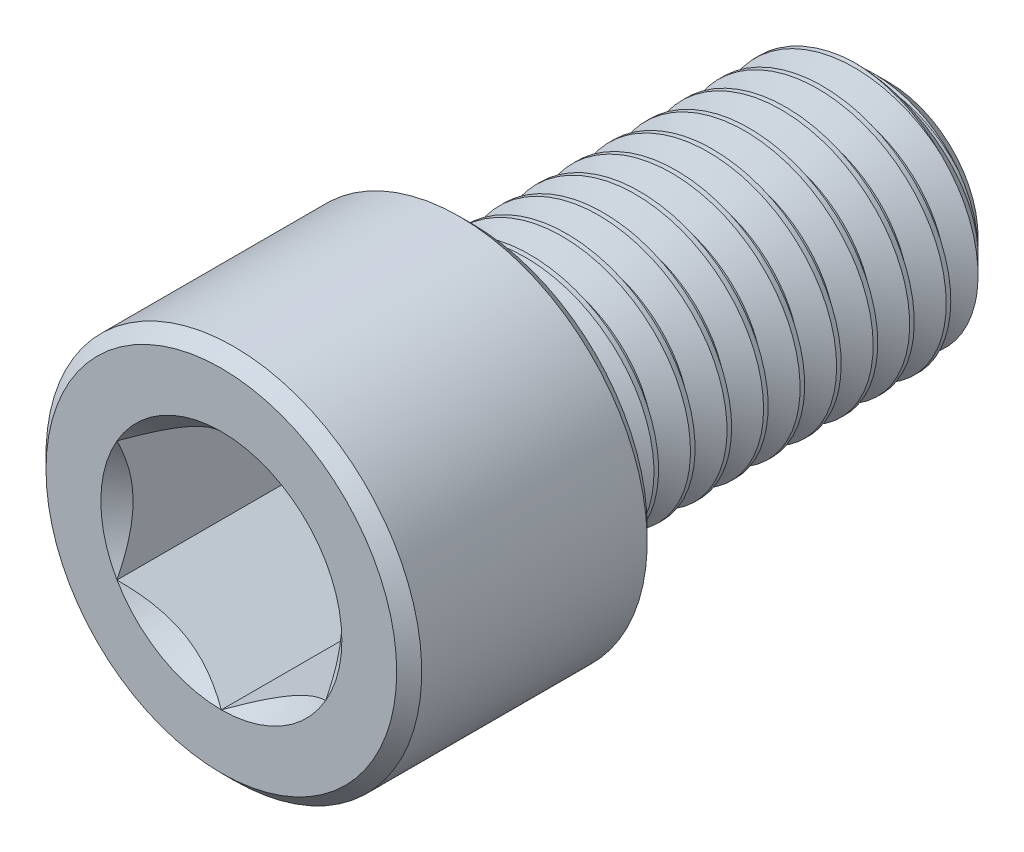
SolidWorks part; units mm, degrees
ref_plane "Front Plane" through (0, 0, 0) normal (0, 0, 1) x (1, 0, 0)
ref_plane "Top Plane" through (0, 0, 0) normal (0, 1, 0) x (1, 0, 0)
ref_plane "Right Plane" through (0, 0, 0) normal (1, 0, 0) x (0, 0, -1)
sketch "Sketch1" plane through (0, 0, 0) normal (1, 0, 0) x (0, 0, -1)
  line L0 (-16, 0) -> (16, 0) construction
  line L1 (16, 0) -> (16, 4.25) construction
  line L2 (16, 4.25) -> (14.25, 6) construction
  line L3 (14.25, 6) -> (14.6875, 6) construction
  line L4 (14.6875, 6) -> (-4, 6) construction
  line L5 (-4, 6) -> (-4, 9) construction
  line L6 (-4, 9) -> (-16, 9) construction
  line L7 (-16, 9) -> (-16, 0) construction
  line L8 (16, 4.25) -> (16, 6) construction
  line L9 (15.8906, 6.1894) -> (16.7656, 4.6739) construction
  line L10 (16.7656, 4.6739) -> (17.6406, 6.1894) construction
  line L11 (17.6406, 6.1894) -> (15.8906, 6.1894) construction
  line L12 (16.7656, 6.1894) -> (16.7656, 6) construction
  line L13 (16.7656, 4.6739) -> (16.7656, 4.8633) construction
  line L14 (16.6562, 4.8633) -> (16.875, 4.8633) construction
  line L15 (16, 6) -> (17.5312, 6) construction
  line L16 (15.9453, 6.0947) -> (17.5859, 6.0947) construction
  line L17 (16, 0) -> (16, -6) construction
  line L18 (-4.6, 9) -> (-4, 8.4) construction
  line L19 (-15.4, 9) -> (-16, 8.4) construction
  line L20 (-4, 6) -> (-4, 0) construction
  line L21 (-4, 3) -> (2.6667, 3) construction
  line L22 (2.6667, 3) -> (9.3333, 3) construction
  line L23 (9.3333, 3) -> (16, 3) construction
  line L24 (2.6667, 3) -> (2.6667, 6) construction
  line L25 (2.6667, 6) -> (2.6667, 9) construction
  line L26 (9.3333, 3) -> (9.3333, 9) construction
  point P0 (-16, 5)
  point P3 (11.625, 6)
  point P4 (0, 0)
  point P18 (9.3333, 6)
  point P22 (16.7656, 4.8633)
  point P24 (14.6875, 6)
  point P25 (16.7656, 6)
  point P28 (16.7656, 6.0947)
  point P29 (11.625, -6)
  point P30 (2.6667, 6)
  point P31 (-10, 9)
  point P37 (-6.1, 9)
  point P38 (-15.1, 9)
  point P45 (2.6667, 3)
  point P46 (9.3333, 3)
  dimension "D1" = 45
  dimension "D2" = 0.2188
  dimension "D3" = 1.75
  dimension "D7" = 0.6
  dimension "D8" = 0.6
  dimension "D9" = 0.6
  dimension "D10" = 0.3
  dimension "D11" = 1.5
  dimension "Drive Size" = 10
  dimension "Head Diameter" = 18
  dimension "Head Height" = 12
  dimension "Thread Pitch" = 1.75
  dimension "Thread Major Diameter" = 12
  dimension "Length" = 20
  dimension "D12" = 1.3125
  dimension "D4" = 4.375
sketch "Sketch2" plane through (0, 0, 0) normal (1, 0, 0) x (0, 0, -1)
  line L0 (-16, 0) -> (-16, 8.4)
  line L1 (-15.4, 9) -> (-4.6, 9)
  line L2 (-4, 8.4) -> (-4, 6)
  line L3 (-4, 6) -> (14.25, 6)
  line L4 (14.25, 6) -> (16, 4.25)
  line L5 (16, 4.25) -> (16, 0)
  line L6 (-4.6, 9) -> (-4, 8.4) construction
  line L7 (16, 0) -> (-16, 0)
  line L8 (-15.4, 9) -> (-16, 8.4) construction
  line L9 (-4.6, 9) -> (-4, 8.4)
  line L10 (-15.4, 9) -> (-16, 8.4)
revolve "Revolve1" add sketch "Sketch2" angle 360 about L7
sketch "Sketch3" plane through (0, 0, 16) normal (0, 0, 1) x (1, 0, 0)
  line L1 (5, -2.8868) -> (5, 2.8868)
  line L2 (5, 2.8868) -> (0, 5.7735)
  line L3 (0, 5.7735) -> (-5, 2.8868)
  line L4 (-5, 2.8868) -> (-5, -2.8868)
  line L5 (-5, -2.8868) -> (0, -5.7735)
  line L6 (0, -5.7735) -> (5, -2.8868)
  circle A0 centre (0, 0) radius 5 construction
extrude "Cut-Extrude1" cut sketch "Sketch3" against normal offset from surface (11 mm away) 1 up to face at (0, 8.4, 4)
sketch "Sketch4" plane through (0, 0, 16) normal (0, 0, 1) x (1, 0, 0)
  circle A0 centre (0, 0) radius 5.7735
extrude "Cut-Extrude2" cut sketch "Sketch4" against normal up to vertex (6 mm away) draft 45 up to point (0, 9, 10)
ref_plane "Plane1" through (0, 0, -14.6875) normal (0, 0, 1) x (1, 0, 0)
split "Split1" bodies to split 106 resulting bodies 107 108 split by face at (0, 8.4, 4)
sketch "Sketch6" plane through (0, 0, -16) normal (0, 0, -1) x (-1, 0, 0)
  circle A0 centre (0, 0) radius 6
curve "Helix/Spiral1" pitch 1.75 height 22.0125 radius 6 centre (0, 0, -16) axis (0, 0, 1) start towards (0, 1, 0)
sketch "Sketch7" plane through (0, 0, 0) normal (1, 0, 0) x (0, 0, -1)
  line L0 (15.9453, 6.0947) -> (17.5859, 6.0947)
  line L1 (17.5859, 6.0947) -> (16.875, 4.8633)
  line L2 (16.875, 4.8633) -> (16.6562, 4.8633)
  line L3 (16.6562, 4.8633) -> (15.9453, 6.0947)
sweep "Cut-Sweep1" cut profiles "Sketch7" path "Helix/Spiral1" align with end faces yes
sketch "Sketch8" plane through (0, 0, 4) normal (0, 0, -1) x (-1, 0, 0)
  circle A0 centre (0, 0) radius 6
extrude "Boss-Extrude1" add sketch "Sketch8" along normal through all draft 45
equation "\"D2@Sketch1\" = \"Thread Pitch@Sketch1\" / 8"
equation "\"D3@Sketch1\"= \"Thread Pitch@Sketch1\""
equation "\"D4@Helix/Spiral1\" = \"Thread Pitch@Sketch1\""
equation "\"D7@Sketch1\" = \"Head Height@Sketch1\" * .05"
equation "\"D8@Sketch1\"=\"D7@Sketch1\""
equation "\"D9@Sketch1\"=\"D7@Sketch1\""
equation "\"D10@Sketch1\"=\"D7@Sketch1\"/2"
equation "\"D11@Sketch1\"=\"D10@Sketch1\"*5"
equation "\"D4@Sketch1\"=\"Thread Pitch@Sketch1\"*2.5"
equation "\"D12@Sketch1\"=\"Thread Pitch@Sketch1\"*.75"
